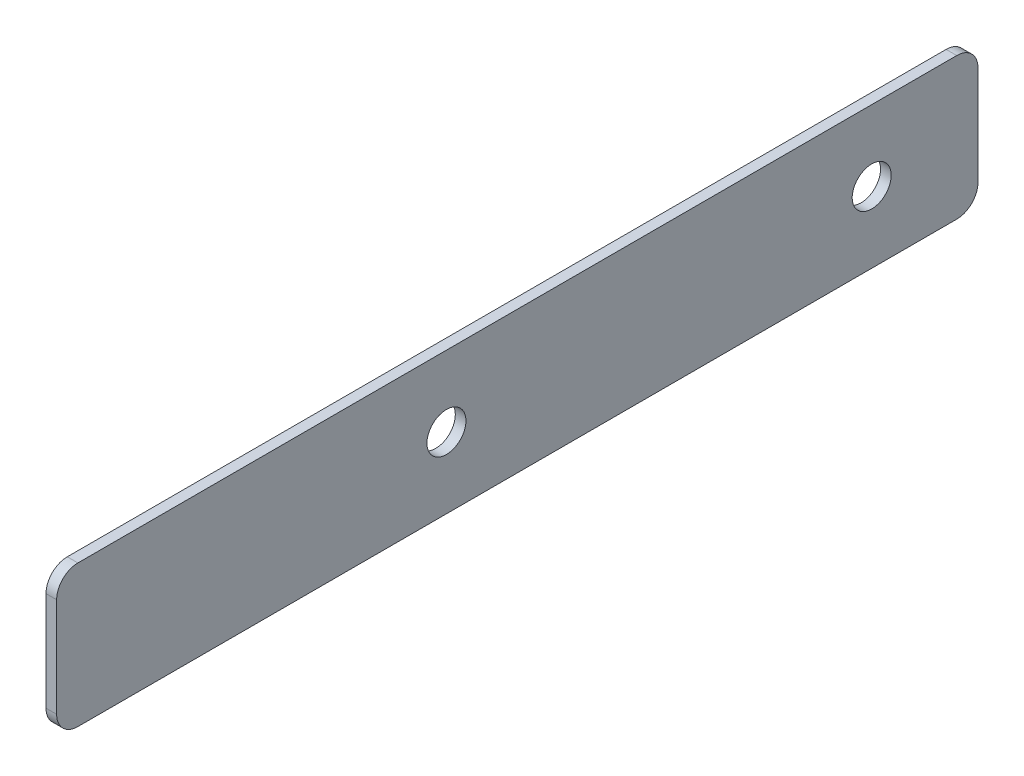
SolidWorks part; units mm, degrees
material "Stal węglowa"
ref_plane "Płaszczyzna przednia" through (0, 0, 0) normal (0, 0, 1) x (1, 0, 0)
ref_plane "Płaszczyzna górna" through (0, 0, 0) normal (0, 1, 0) x (1, 0, 0)
ref_plane "Płaszczyzna prawa" through (0, 0, 0) normal (1, 0, 0) x (0, 0, -1)
sketch "Szkic1" plane through (0, 0, 0) normal (1, 0, 0) x (0, 0, -1)
  line L1 (-65, 10) -> (65, 10)
  line L2 (-65, 10) -> (-65, -10)
  line L3 (-65, -10) -> (65, -10)
  line L4 (65, 10) -> (65, -10)
  line L5 (-65, 10) -> (65, -10) construction
  line L6 (-65, -10) -> (65, 10) construction
  point P0 (0, 0)
  dimension "D1" = 20
  dimension "D2" = 130
base flange "Odgięcie bazowe1" sketch "Szkic1" thickness 1.5 reverse thickness direction no parameters "D1"=2.6
hole_wizard "Otwór pod śrubę M51" positions "Szkic6" profile "Szkic7" hole size "M5" standard "ISO"
sketch "Szkic6" plane through (0, 0, 0) normal (1, 0, 0) x (0, 0, -1)
  line L0 (65, -10) -> (65, 10) construction
  point P0 (-10, 0)
  point P2 (50, 0)
  dimension "D1" = 60
  dimension "D2" = 15
sketch "Szkic7" plane through (0, 0, 10) normal (0, 1, 0) x (0, 0, -1)
  line L0 (0, 0) -> (0, 11.6524)
  line L1 (0, 11.6524) -> (2.75, 10)
  line L2 (2.75, 10) -> (2.75, 0)
  line L5 (2.75, 0) -> (0, 0)
  line L10 (0, 11.6524) -> (-2.75, 10) construction
  line L11 (0, -6.35) -> (0, 107.95) construction
  dimension "Średnica otworu" = 5.5
  dimension "Głębokość otworu" = 10
  dimension "Kąt wiertła" = 118
fillet "Zaokrąglenie1" radius 3 4 edges at (-0.75, -10, -65) (-0.75, 10, -65) (-0.75, -10, 65) (-0.75, 10, 65)
sketch "Linie zgięcia1" [suppressed] plane through (0, 0, 0) normal (0, 1, 0) x (1, 0, 0)
sketch "Ramka-graniczna1" [suppressed] plane through (0, 0, 0) normal (0, 1, 0) x (1, 0, 0)
sheet metal parameters "Arkusz blachy2" thickness 1.5 parameters "D1"=2.6
flat pattern "Rozłożony model2" [suppressed]
sketch "Linie zgięcia2" plane through (0, 0, 0) normal (0, 1, 0) x (1, 0, 0)
sketch3d "Ramka-graniczna2" [suppressed]
  line L0 (60, -15, 0) -> (-60, -15, 0) construction
  line L1 (60, 15, 0) -> (-60, 15, 0) construction
  line L2 (60, -15, 0) -> (60, 15, 0) construction
  line L3 (-60, -15, 0) -> (-60, 15, 0) construction
sheet metal parameters "Arkusz blachy3" thickness 1.5 parameters "D1"=2.6
flat pattern "Rozłożony model2"
sketch "Linie zgięcia2" plane through (0, 0, 0) normal (0, 1, 0) x (1, 0, 0)
sketch3d "Ramka-graniczna2" [suppressed]
  line L0 (-65, 10, 0) -> (65, 10, 0) construction
  line L1 (-65, -10, 0) -> (65, -10, 0) construction
  line L2 (-65, 10, 0) -> (-65, -10, 0) construction
  line L3 (65, 10, 0) -> (65, -10, 0) construction
